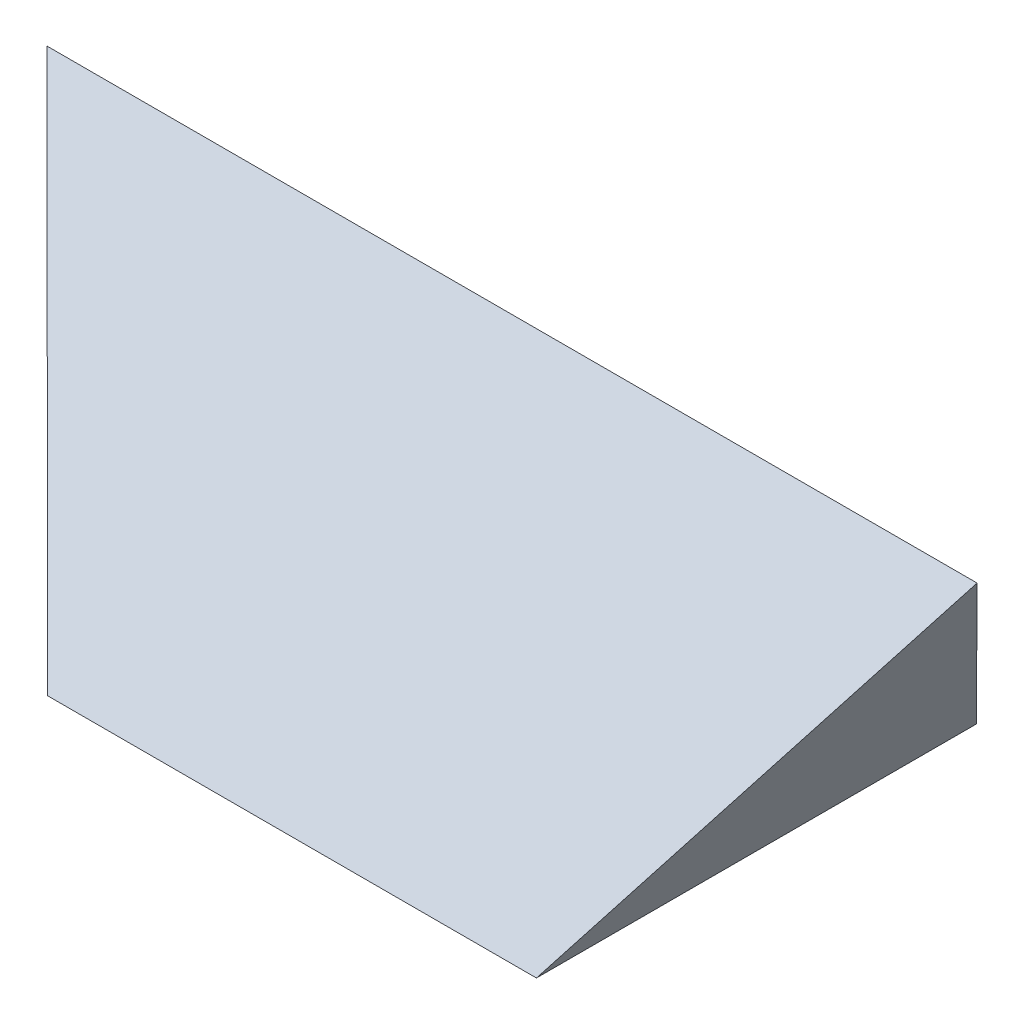
SolidWorks part; units mm, degrees
ref_plane "Front Plane" through (0, 0, 0) normal (0, 0, 1) x (1, 0, 0)
ref_plane "Top Plane" through (0, 0, 0) normal (0, 1, 0) x (1, 0, 0)
ref_plane "Right Plane" through (0, 0, 0) normal (1, 0, 0) x (0, 0, -1)
sketch "Sketch1" plane through (0, 0, 0) normal (0, 0, 1) x (1, 0, 0)
  line L0 (15, 0) -> (-15, 0)
  line L1 (0, 0) -> (0, 42.0276) construction
  line L2 (28.5433, 21.0138) -> (-28.5433, 21.0138)
  line L3 (-28.5433, 21.0138) -> (-15, 0)
  line L4 (28.5433, 21.0138) -> (15, 0)
  point P4 (0, 0)
  point P9 (0, 21.0138)
extrude "Boss-Extrude2" add sketch "Sketch1" along normal blind 27 contours L2 L3 L0 L4
sketch "Sketch3" plane through (0, 0, 0) normal (1, 0, 0) x (0, 0, -1)
  line L1 (-13.5, 21.0138) -> (-27, 0)
  line L2 (-27, 0) -> (-27, 21.0138)
  line L3 (-27, 21.0138) -> (-13.5, 21.0138)
  line L4 (-13.5, 21.0138) -> (0, 0)
  line L5 (0, 0) -> (0, 21.0138)
  line L6 (0, 21.0138) -> (-13.5, 21.0138)
extrude "Cut-Extrude4" cut sketch "Sketch3" against normal blind 37 and the other way blind 37 contours L4 L5 L6
sketch "Sketch4" plane through (0, 0, 0) normal (1, 0, 0) x (0, 0, -1)
  line L0 (-13.5, 21.0138) -> (-27, 0)
  line L1 (-27, 21.0138) -> (-13.5, 21.0138)
  line L2 (-27, 21.0138) -> (-27, 0)
extrude "Cut-Extrude5" cut sketch "Sketch4" against normal blind 37 and the other way blind 37 contours L2 L0 L1
